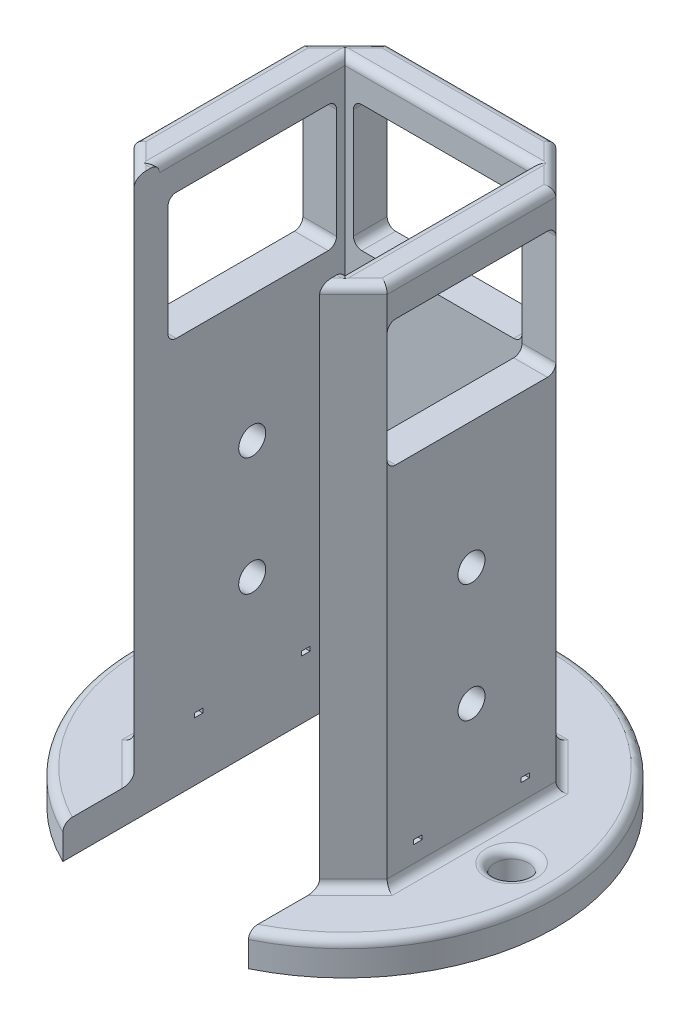
SolidWorks part; units mm, degrees
ref_plane "Front Plane" through (0, 0, 0) normal (0, 0, 1) x (1, 0, 0)
ref_plane "Top Plane" through (0, 0, 0) normal (0, 1, 0) x (1, 0, 0)
ref_plane "Right Plane" through (0, 0, 0) normal (1, 0, 0) x (0, 0, -1)
sketch "Sketch1" plane through (0, 0, 0) normal (0, 1, 0) x (1, 0, 0)
  line L1 (0, 0) -> (30, 0)
  line L2 (0, 0) -> (0, 30)
  line L3 (0, 30) -> (30, 30)
  line L4 (30, 0) -> (30, 30)
  dimension "D1" = 30
  dimension "D2" = 30
extrude "Boss-Extrude1" add sketch "Sketch1" along normal blind 62
shell "Shell1" thickness 4 removed face at (15, 0, -15) removed face at (15, 62, -15)
sketch "Sketch2" plane through (30, 0, 0) normal (1, 0, 0) x (0, 0, -1)
  line L0 (0, 0) -> (30, 0) construction
  circle A0 centre (15, 14) radius 1.6
  circle A2 centre (15, 28) radius 1.6
  point P8 (15, 0)
  dimension "D1" = 3.2
  dimension "D2" = 3.2
  dimension "D3" = 14
  dimension "D4" = 14
extrude "Cut-Extrude1" cut sketch "Sketch2" against normal blind 62
sketch "Sketch3" plane through (0, 0, 0) normal (0, -1, 0) x (1, 0, 0)
  line L0 (26, -26) -> (4, -26) construction
  line L9 (30, 0) -> (30, -30) construction
  line L11 (26, -4) -> (26, -26) construction
  line L12 (4, -26) -> (4, -4) construction
  line L13 (4, -4) -> (26, -4) construction
  line L14 (26, -26) -> (4, -26)
  line L15 (26, -4) -> (26, -26)
  line L16 (4, -26) -> (4, -4)
  line L17 (4, -4) -> (26, -4)
  circle A0 centre (15, -15) radius 25
  circle A1 centre (34.75, -15) radius 2
  circle A8 centre (15, -34.75) radius 2
  circle A9 centre (-4.75, -15) radius 2
  circle A10 centre (15, 4.75) radius 2
  point P7 (26, -15)
  point P15 (15, -26)
  point P23 (16.25, -11.25)
  point P24 (15, -15)
  dimension "D1" = 50
  dimension "D2" = 4
  dimension "D3" = 4.75
  dimension "D4" = 4
extrude "Boss-Extrude2" add sketch "Sketch3" along normal blind 4
pattern_circular "CirPattern1" count 2 over 90 about axis through (15, -4, -15) along (0, 1, 0) of "Cut-Extrude1"
chamfer "Chamfer1" distance 5 angle 45 4 edges at (0, 31, 0) (30, 31, 0) (30, 31, -30) (0, 31, -30)
fillet "Fillet1" radius 1 12 edges at (15, 62, -4) (26, 62, -15) (15, 62, -26) (4, 62, -15) (2.5, 62, -27.5) (15, 62, -30) (27.5, 62, -27.5) (30, 62, -15) (27.5, 62, -2.5) (15, 62, 0) (2.5, 62, -2.5) (0, 62, -15)
fillet "Fillet2" radius 1 13 edges at (34.75, 0, -17) (15, 0, -40) (2.5, 0, -2.5) (15, 0, 0) (27.5, 0, -2.5) (30, 0, -15) (27.5, 0, -27.5) (15, 0, -30) (2.5, 0, -27.5) (0, 0, -15) (15, 0, 2.75) (-4.75, 0, -17) (15, 0, -36.75)
sketch "Sketch4" plane through (4, 0, 0) normal (1, 0, 0) x (0, 0, -1)
  line L0 (8.14, 3.46) -> (9.16, 3.46)
  line L1 (9.16, 3.46) -> (9.16, 2.95)
  line L2 (9.16, 2.95) -> (8.14, 2.95)
  line L3 (8.14, 2.95) -> (8.14, 3.46)
  line L12 (21.86, 2.95) -> (21.86, 3.46)
  line L13 (21.86, 3.46) -> (20.84, 3.46)
  line L14 (20.84, 3.46) -> (20.84, 2.95)
  line L15 (20.84, 2.95) -> (21.86, 2.95)
extrude "Cut-Extrude2" cut sketch "Sketch4" against normal through all both and the other way through all
pattern_circular "CirPattern2" count 2 over 90 about axis through (15, -4, -15) along (0, -1, 0) of "Cut-Extrude2"
sketch "Sketch5" plane through (0, 62, 0) normal (0, 1, 0) x (1, 0, 0)
  line L1 (4, 4) -> (26, 4)
  line L2 (4, 4) -> (4, -10.9141)
  line L3 (4, -10.9141) -> (26, -10.9141)
  line L4 (26, 4) -> (26, -10.9141)
extrude "Cut-Extrude3" cut sketch "Sketch5" against normal through all
sketch "Sketch6" plane through (0, 0, 0) normal (-1, 0, 0) x (0, 0, 1)
  line L0 (-5, 1) -> (-5, 61) construction
  line L1 (-25, 58) -> (-5, 58)
  line L2 (-25, 58) -> (-25, 43)
  line L3 (-25, 43) -> (-5, 43)
  line L4 (-5, 58) -> (-5, 43)
  line L5 (-5, 61) -> (-25, 61) construction
  dimension "D1" = 18
  dimension "D2" = 3
extrude "Cut-Extrude4" cut sketch "Sketch6" against normal through all and the other way through all
sketch "Sketch7" plane through (0, 0, -30) normal (0, 0, -1) x (-1, 0, 0)
  line L0 (-5, 1) -> (-5, 61) construction
  line L1 (-25, 58) -> (-5, 58)
  line L2 (-25, 58) -> (-25, 43)
  line L3 (-25, 43) -> (-5, 43)
  line L4 (-5, 58) -> (-5, 43)
  line L5 (-5, 61) -> (-25, 61) construction
  dimension "D1" = 18
  dimension "D2" = 3
extrude "Cut-Extrude5" cut sketch "Sketch7" against normal through all contours L1 L4 L3 L2
fillet "Fillet4" radius 1 12 edges at (2, 43, -5) (2, 58, -5) (2, 58, -25) (2, 43, -25) (25, 43, -28) (25, 58, -28) (28, 58, -25) (28, 43, -25) (5, 43, -28) (5, 58, -28) (28, 58, -5) (28, 43, -5)
